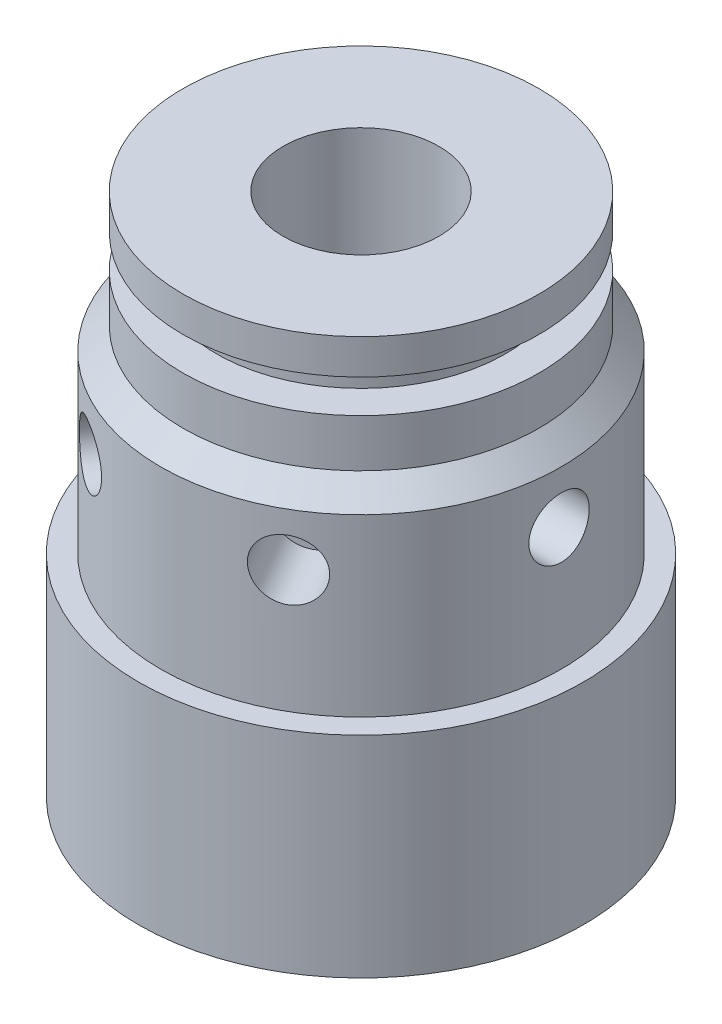
SolidWorks part; units mm, degrees
ref_plane "Front Plane" through (0, 0, 0) normal (0, 0, 1) x (1, 0, 0)
ref_plane "Top Plane" through (0, 0, 0) normal (0, 1, 0) x (1, 0, 0)
ref_plane "Right Plane" through (0, 0, 0) normal (1, 0, 0) x (0, 0, -1)
sketch "Sketch1" plane through (0, 0, 0) normal (0, 0, 1) x (1, 0, 0)
  line L0 (0, -18.6906) -> (15.875, -18.6906)
  line L1 (15.875, -18.6906) -> (15.875, -3.6906)
  line L2 (15.875, -3.6906) -> (14.29, -3.6906)
  line L3 (12.7, 10.3994) -> (12.7, 13.8094)
  line L4 (12.7, 13.8094) -> (10.3188, 13.8094)
  line L5 (10.3188, 13.8094) -> (10.3188, 16.1906)
  line L6 (10.3188, 16.1906) -> (12.7, 16.1906)
  line L7 (12.7, 16.1906) -> (12.7, 18.6906)
  line L13 (0, 18.6906) -> (0, -18.6906)
  line L14 (0, -8.095) -> (0, 15.2312) construction
  line L15 (12.7, 17.1677) -> (12.7, -7.7109) construction
  line L16 (10.3188, 15) -> (12.7, 15) construction
  line L19 (14.29, -3.6906) -> (14.29, 8.8094)
  line L20 (14.29, 8.8094) -> (12.7, 10.3994)
  line L21 (0, 18.6906) -> (12.7, 18.6906)
  line L22 (10.3188, 13.8094) -> (10.3188, -3.6906) construction
  line L23 (10.3188, -3.6906) -> (14.29, -3.6906) construction
  point P18 (0, 0)
  dimension "D1" = 12.7
  dimension "D2" = 12.5
  dimension "D3" = 31.75
  dimension "D4" = 15
  dimension "D5" = 135
  dimension "D6" = 2.5
  dimension "D7" = 17.5
  dimension "D8" = 1.59
  dimension "D9" = 2.3812
revolve "Revolve1" add sketch "Sketch1" angle 360 about L14
sketch "Sketch2" plane through (0, 0, 0) normal (1, 0, 0) x (0, 0, -1)
  line L0 (0, -3.6906) -> (0, -18.6906) construction
  line L1 (15.875, -3.6906) -> (-15.875, -3.6906) construction
  line L2 (-15.875, -18.6906) -> (15.875, -18.6906) construction
  circle A0 centre (0, -11.1906) radius 5.5562
  dimension "D1" = 11.1125
ref_plane "Plane1" through (14.29, 0, 0) normal (1, 0, 0) x (0, 0, -1)
sketch "Sketch4" plane through (14.29, 0, 0) normal (1, 0, 0) x (0, 0, -1)
  line L0 (0, -3.6906) -> (0, 13.8094) construction
  line L1 (15.875, -3.6906) -> (-15.875, -3.6906) construction
  line L2 (12.7, 13.8094) -> (-12.7, 13.8094) construction
  circle A0 centre (0, 5.0594) radius 2.15
  dimension "D1" = 4.3
extrude "Cut-Extrude3" cut sketch "Sketch4" against normal blind 5
pattern_circular "CirPattern1" count 6 over 360 about axis through (0, -8.095, 0) along (0, -1, 0) of "Cut-Extrude3"
sketch "Sketch6" plane through (0, 18.6906, 0) normal (0, 1, 0) x (1, 0, 0)
  circle A0 centre (0, 0) radius 5.5626
  dimension "D1" = 11.1252
extrude "Cut-Extrude4" cut sketch "Sketch6" against normal up to surface (37.3813 mm away) up to face at (0, -18.6906, -15.875)
